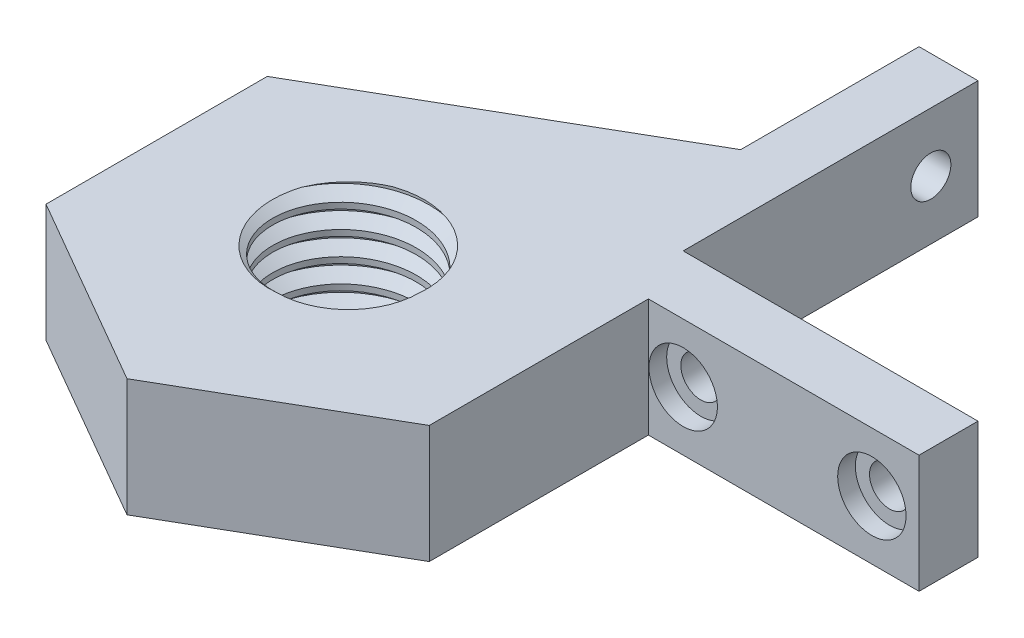
SolidWorks part; units mm, degrees
ref_plane "Ebene vorne" through (0, 0, 0) normal (0, 0, 1) x (1, 0, 0)
ref_plane "Ebene oben" through (0, 0, 0) normal (0, 1, 0) x (1, 0, 0)
ref_plane "Ebene rechts" through (0, 0, 0) normal (1, 0, 0) x (0, 0, -1)
sketch "Skizze1" plane through (0, 0, 0) normal (0, 1, 0) x (1, 0, 0)
  line L0 (0, 0) -> (-14.2, -14.2) construction
  line L1 (-14.2, -14.2) -> (-14.2, 10.1255) construction
  line L2 (-14.2, -14.2) -> (7.3874, -14.2) construction
  line L9 (0, 0) -> (0, 25)
  line L10 (0, 0) -> (25, 0)
  line L11 (0, 25) -> (-5, 25)
  line L12 (-5, 25) -> (-5, 9.8755)
  line L13 (-5, 9.8755) -> (-30.45, -4.8181)
  line L14 (-30.45, -4.8181) -> (-30.45, -23.5819)
  line L15 (-30.45, -23.5819) -> (-14.2, -32.9639)
  line L16 (2.05, -23.5819) -> (2.05, -5)
  line L17 (2.05, -5) -> (25, -5)
  line L18 (25, -5) -> (25, 0)
  line L19 (-14.2, -32.9639) -> (2.05, -23.5819)
  circle A0 centre (-14.2, -14.2) radius 6.1
  dimension "D2" = 12.2
  dimension "D4" = 45
  dimension "D5" = 25
  dimension "D6" = 25
  dimension "D7" = 5
  dimension "D8" = 5
  dimension "D13" = 14.2
extrude "Aufsatz-Linear austragen1" add sketch "Skizze1" along normal blind 10
fillet "Verrundung1" [suppressed] radius 5
sketch "Skizze3" plane through (0, 0, 5) normal (0, 0, 1) x (1, 0, 0)
  line L0 (2.05, 5) -> (25, 5) construction
  line L1 (2.05, 10) -> (2.05, 0) construction
  line L2 (25, 10) -> (25, 0) construction
  line L3 (0, 0) -> (0, 10) construction
  circle A0 centre (5, 5) radius 1.7
  circle A1 centre (21, 5) radius 1.7
  dimension "D1" = 3.4
  dimension "D3" = 21
  dimension "D2" = 5
extrude "Schnitt-Linear austragen1" cut sketch "Skizze3" against normal up to next contours A1 | A0 region at (21, 5, 5)
sketch "Skizze5" plane through (0, 0, 5) normal (0, 0, 1) x (1, 0, 0)
  circle A0 centre (5, 5) radius 2.9
  circle A1 centre (21, 5) radius 2.9
  dimension "D1" = 5.8
extrude "Schnitt-Linear austragen2" cut sketch "Skizze5" against normal blind 1.5 and the other way blind 7
sketch "Skizze6" plane through (-5, 0, 0) normal (-1, 0, 0) x (0, 0, 1)
  line L0 (-9.8755, 5) -> (-25, 5) construction
  line L1 (-9.8755, 10) -> (-9.8755, 0) construction
  line L2 (-25, 10) -> (-25, 0) construction
  circle A0 centre (-21, 5) radius 1.7
  dimension "D1" = 3.4
  dimension "D2" = 21
extrude "Schnitt-Linear austragen3" cut sketch "Skizze6" against normal up to next
sketch "Skizze7" plane through (-5, 0, 0) normal (-1, 0, 0) x (0, 0, 1)
  circle A0 centre (-21, 5) radius 2.9
  dimension "D1" = 5.8
extrude "Schnitt-Linear austragen4" cut sketch "Skizze7" against normal blind 1.5
sketch "Skizze8" plane through (0, 0, 0) normal (0, -1, 0) x (1, 0, 0)
  line L0 (-30.45, 23.5819) -> (-30.45, 4.8181)
  line L1 (-30.45, 4.8181) -> (-5, -9.8755)
  line L3 (0, 0) -> (-5, -9.8755)
  line L4 (0, 0) -> (2.05, 5)
  line L5 (2.05, 5) -> (2.05, 23.5819)
  line L6 (2.05, 23.5819) -> (-14.2, 32.9639)
  line L9 (-30.45, 23.5819) -> (-14.2, 32.9639)
  line L12 (2.05, 5) -> (2.05, 23.5819)
  line L13 (2.05, 5) -> (2.05, 23.5819)
  line L20 (0, 0) -> (25, 0)
  line L21 (25, 0) -> (25, 5)
  line L22 (25, 5) -> (2.05, 5)
  line L24 (2.05, 23.5819) -> (-14.2, 32.9639)
  line L25 (2.05, 23.5819) -> (-14.2, 32.9639)
  line L26 (-14.2, 32.9639) -> (-30.45, 23.5819)
  line L27 (-30.45, 23.5819) -> (-30.45, 4.8181)
  line L28 (-30.45, 23.5819) -> (-30.45, 4.8181)
  line L29 (-30.45, 4.8181) -> (-5, -9.8755)
  line L30 (-30.45, 4.8181) -> (-5, -9.8755)
  line L31 (0, 0) -> (25, 0)
  line L32 (25, 0) -> (25, 5)
  line L33 (25, 5) -> (2.05, 5)
  line L34 (-5, -9.8755) -> (-5, -25)
  line L35 (-5, -9.8755) -> (-5, -25)
  line L36 (-5, -25) -> (0, -25)
  line L37 (-5, -25) -> (0, -25)
  line L38 (0, -25) -> (0, 0)
  line L39 (0, -25) -> (0, 0)
  dimension "D1" = 0
extrude "Aufsatz-Linear austragen2" [suppressed] add sketch "Skizze8" along normal blind 2
fillet "Verrundung2" [suppressed] radius 2
sketch "Skizze9" [suppressed] plane through (0, -2, 0) normal (0, -1, 0) x (1, 0, 0)
  line L0 (-25.45, 20.6952) -> (-2.95, 7.7048) construction
  line L1 (-23.45, 19.5405) -> (-14.2, 24.881)
  line L2 (-14.2, 24.881) -> (-4.95, 19.5405)
  line L3 (-4.95, 19.5405) -> (-4.95, 8.8595)
  line L4 (-4.95, 8.8595) -> (-14.2, 3.519)
  line L5 (-14.2, 3.519) -> (-23.45, 8.8595)
  line L6 (-23.45, 8.8595) -> (-23.45, 19.5405)
  line L7 (-25.45, 20.6952) -> (-14.2, 27.1904) construction
  line L8 (-14.2, 27.1904) -> (-2.95, 20.6952) construction
  line L9 (-2.95, 20.6952) -> (-2.95, 7.7048) construction
  line L10 (-2.95, 7.7048) -> (-14.2, 1.2096) construction
  line L11 (-14.2, 1.2096) -> (-25.45, 7.7048) construction
  line L12 (-25.45, 7.7048) -> (-25.45, 20.6952) construction
  dimension "D1" = 2
extrude "Aufsatz-Linear austragen3" [suppressed] add sketch "Skizze9" against normal blind 1 contours L0 L8 L7 L4 L5 L6 | L9 L0 L1 L2 L3 L11 L10
fillet "Verrundung3" [suppressed] radius 1
thread "Gewinde1" pitch 2 method cut profile "Gewindeprofil1" start angle 0, offset 5, length 20, pitch 2, diameter 12.2
ref_plane "Ebene1" through (-20.3, 15, 14.2) normal (0, 0, 1) x (-1, 0, 0)
sketch "Gewindeprofil1" plane through (-20.3, 15, 14.2) normal (0, 0, 1) x (-1, 0, 0)
  line L0 (0, 0) -> (0, 2) construction
  line L1 (0, 0) -> (1.0825, 0.625)
  line L2 (1.0825, 0.625) -> (1.0825, 0.875)
  line L3 (1.0825, 0.875) -> (0, 1.5)
  line L4 (1.0825, 0.75) -> (0, 0.75) construction
  line L11 (0, 0) -> (0, 1.5)
  point P2 (0, 0)
  dimension "Pitch" = 2
  dimension "Profile_Angle" = 60
  dimension "Profile_Land" = 0.25
  dimension "Profile_Height" = 1.0825
move or copy body "Körper-Verschieben/Kopieren1" [suppressed] bodies to move or copy 108 copy no rotation origin (0, 5.0005, 3.9819) rotation axis (1, 0, 0) rotation angle 90
